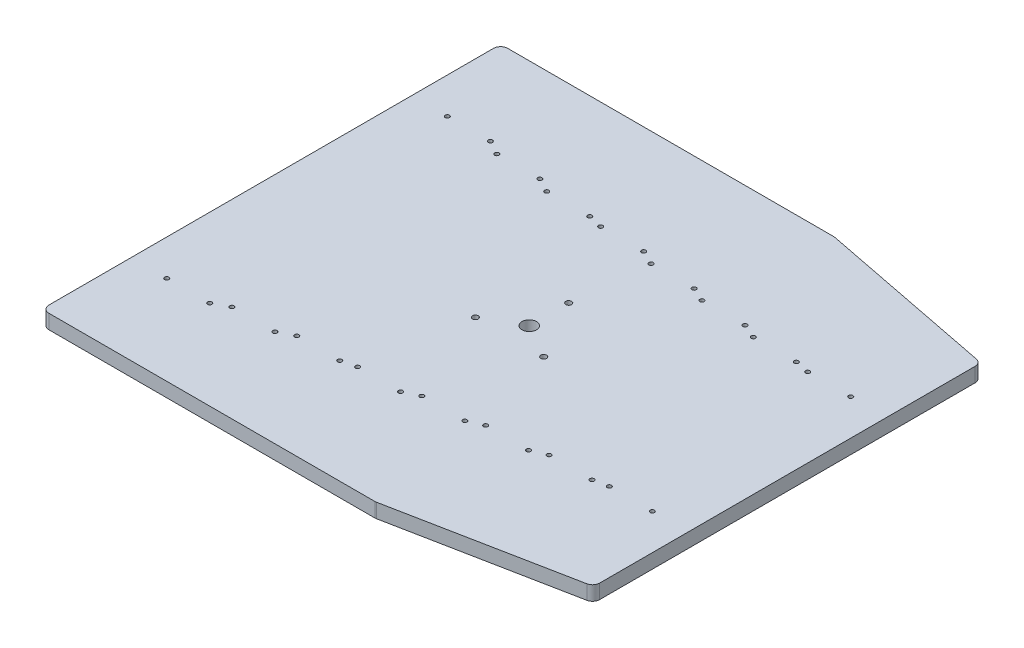
SolidWorks part; units mm, degrees
material "AISI Type 316L stainless steel"
ref_plane "Front Plane" through (0, 0, 0) normal (0, 0, 1) x (1, 0, 0)
ref_plane "Top Plane" through (0, 0, 0) normal (0, 1, 0) x (1, 0, 0)
ref_plane "Right Plane" through (0, 0, 0) normal (1, 0, 0) x (0, 0, -1)
sketch "Sketch1" plane through (0, 0, 0) normal (0, 1, 0) x (1, 0, 0)
  line L1 (-228.6, -203.2) -> (228.6, -203.2)
  line L2 (-228.6, -203.2) -> (-228.6, 203.2)
  line L3 (-228.6, 203.2) -> (228.6, 203.2)
  line L4 (228.6, -203.2) -> (228.6, 203.2)
  line L5 (-228.6, -203.2) -> (228.6, 203.2) construction
  line L6 (-228.6, 203.2) -> (228.6, -203.2) construction
  point P0 (0, 0)
  dimension "D1" = 457.2
  dimension "D2" = 406.4
extrude "Boss-Extrude1" add sketch "Sketch1" along normal blind 12.7
hole_wizard "#6 Clearance Hole1" positions "Sketch2" profile "Sketch3" hole size "#6" standard "ANSI Inch" end condition through all
sketch "Sketch2" plane through (0, 0, 0) normal (0, -1, 0) x (-1, 0, 0)
  line L0 (-228.6, 0) -> (228.6, 0) construction
  line L1 (-228.6, -203.2) -> (-228.6, 203.2) construction
  line L2 (228.6, 203.2) -> (228.6, -203.2) construction
  point P0 (-196.85, 87.8764)
  point P3 (-158.75, 87.8764)
  point P6 (-146.05, 90.4545)
  point P9 (-107.95, 90.4545)
  point P12 (-95.25, 95.8317)
  point P15 (-57.15, 95.8317)
  point P18 (-44.45, 101.5035)
  point P21 (-6.35, 101.5035)
  point P24 (6.35, 107.6173)
  point P27 (44.45, 107.6173)
  point P30 (57.15, 110.711)
  point P33 (95.25, 110.711)
  point P36 (107.95, 117.3404)
  point P39 (146.05, 117.3404)
  point P42 (158.75, 124.2644)
  point P45 (196.85, 124.2644)
  point P56 (196.85, -124.2644)
  point P57 (158.75, -124.2644)
  point P58 (146.05, -117.3404)
  point P59 (107.95, -117.3404)
  point P60 (95.25, -110.711)
  point P61 (57.15, -110.711)
  point P62 (44.45, -107.6173)
  point P63 (6.35, -107.6173)
  point P64 (-6.35, -101.5035)
  point P65 (-44.45, -101.5035)
  point P66 (-57.15, -95.8317)
  point P67 (-95.25, -95.8317)
  point P68 (-107.95, -90.4545)
  point P69 (-146.05, -90.4545)
  point P70 (-158.75, -87.8764)
  point P71 (-196.85, -87.8764)
sketch "Sketch3" plane through (196.85, 0, -87.8764) normal (1, 0, 0) x (0, 0, -1)
  line L0 (0, 0) -> (0, 12.7)
  line L1 (0, 12.7) -> (1.8986, 12.7)
  line L2 (1.8986, 12.7) -> (1.8986, 0)
  line L5 (1.8986, 0) -> (0, 0)
  line L11 (0, -6.35) -> (0, 107.95) construction
  dimension "Thru Hole Dia." = 3.7973
  dimension "Thru Hole Depth" = 12.7
sketch "Sketch4" plane through (0, 12.7, 0) normal (0, 1, 0) x (1, 0, 0)
  line L0 (-196.85, 124.2644) -> (-158.75, 124.2644) construction
  line L1 (-196.85, 130.6144) -> (-158.75, 130.6144)
  line L2 (-196.85, 117.9144) -> (-158.75, 117.9144)
  line L3 (-146.05, 117.3404) -> (-107.95, 117.3404) construction
  line L4 (-146.05, 123.6904) -> (-107.95, 123.6904)
  line L5 (-146.05, 110.9904) -> (-107.95, 110.9904)
  line L6 (-95.25, 110.711) -> (-57.15, 110.711) construction
  line L7 (-95.25, 117.061) -> (-57.15, 117.061)
  line L8 (-95.25, 104.361) -> (-57.15, 104.361)
  line L9 (-44.45, 107.6173) -> (-6.35, 107.6173) construction
  line L10 (-44.45, 113.9673) -> (-6.35, 113.9673)
  line L11 (-44.45, 101.2673) -> (-6.35, 101.2673)
  line L12 (6.35, 101.5035) -> (44.45, 101.5035) construction
  line L13 (6.35, 107.8535) -> (44.45, 107.8535)
  line L14 (6.35, 95.1535) -> (44.45, 95.1535)
  line L15 (57.15, 95.8317) -> (95.25, 95.8317) construction
  line L16 (57.15, 102.1817) -> (95.25, 102.1817)
  line L17 (57.15, 89.4817) -> (95.25, 89.4817)
  line L18 (107.95, 90.4545) -> (146.05, 90.4545) construction
  line L19 (107.95, 96.8045) -> (146.05, 96.8045)
  line L20 (107.95, 84.1045) -> (146.05, 84.1045)
  line L21 (158.75, 87.8764) -> (196.85, 87.8764) construction
  line L22 (158.75, 94.2264) -> (196.85, 94.2264)
  line L23 (158.75, 81.5264) -> (196.85, 81.5264)
  line L24 (-228.6, 0) -> (228.6, 0) construction
  line L25 (-228.6, 203.2) -> (-228.6, -203.2) construction
  line L26 (228.6, -203.2) -> (228.6, 203.2) construction
  line L27 (-196.85, -124.2644) -> (-158.75, -124.2644) construction
  line L28 (-196.85, -130.6144) -> (-158.75, -130.6144)
  line L29 (-196.85, -117.9144) -> (-158.75, -117.9144)
  line L30 (-146.05, -117.3404) -> (-107.95, -117.3404) construction
  line L31 (-146.05, -123.6904) -> (-107.95, -123.6904)
  line L32 (-146.05, -110.9904) -> (-107.95, -110.9904)
  line L33 (-95.25, -110.711) -> (-57.15, -110.711) construction
  line L34 (-95.25, -117.061) -> (-57.15, -117.061)
  line L35 (-95.25, -104.361) -> (-57.15, -104.361)
  line L36 (-44.45, -107.6173) -> (-6.35, -107.6173) construction
  line L37 (-44.45, -113.9673) -> (-6.35, -113.9673)
  line L38 (-44.45, -101.2673) -> (-6.35, -101.2673)
  line L39 (6.35, -101.5035) -> (44.45, -101.5035) construction
  line L40 (6.35, -107.8535) -> (44.45, -107.8535)
  line L41 (6.35, -95.1535) -> (44.45, -95.1535)
  line L42 (57.15, -95.8317) -> (95.25, -95.8317) construction
  line L43 (57.15, -102.1817) -> (95.25, -102.1817)
  line L44 (57.15, -89.4817) -> (95.25, -89.4817)
  line L45 (107.95, -90.4545) -> (146.05, -90.4545) construction
  line L46 (107.95, -96.8045) -> (146.05, -96.8045)
  line L47 (107.95, -84.1045) -> (146.05, -84.1045)
  line L48 (158.75, -87.8764) -> (196.85, -87.8764) construction
  line L49 (158.75, -94.2264) -> (196.85, -94.2264)
  line L50 (158.75, -81.5264) -> (196.85, -81.5264)
  arc A0 (-196.85, 130.6144) -> (-196.85, 117.9144) centre (-196.85, 124.2644) ccw
  arc A1 (-158.75, 117.9144) -> (-158.75, 130.6144) centre (-158.75, 124.2644) ccw
  arc A2 (-146.05, 123.6904) -> (-146.05, 110.9904) centre (-146.05, 117.3404) ccw
  arc A3 (-107.95, 110.9904) -> (-107.95, 123.6904) centre (-107.95, 117.3404) ccw
  arc A6 (-95.25, 117.061) -> (-95.25, 104.361) centre (-95.25, 110.711) ccw
  arc A7 (-57.15, 104.361) -> (-57.15, 117.061) centre (-57.15, 110.711) ccw
  arc A8 (-44.45, 113.9673) -> (-44.45, 101.2673) centre (-44.45, 107.6173) ccw
  arc A9 (-6.35, 101.2673) -> (-6.35, 113.9673) centre (-6.35, 107.6173) ccw
  arc A10 (6.35, 107.8535) -> (6.35, 95.1535) centre (6.35, 101.5035) ccw
  arc A11 (44.45, 95.1535) -> (44.45, 107.8535) centre (44.45, 101.5035) ccw
  arc A12 (57.15, 102.1817) -> (57.15, 89.4817) centre (57.15, 95.8317) ccw
  arc A13 (95.25, 89.4817) -> (95.25, 102.1817) centre (95.25, 95.8317) ccw
  arc A14 (107.95, 96.8045) -> (107.95, 84.1045) centre (107.95, 90.4545) ccw
  arc A15 (146.05, 84.1045) -> (146.05, 96.8045) centre (146.05, 90.4545) ccw
  arc A16 (158.75, 94.2264) -> (158.75, 81.5264) centre (158.75, 87.8764) ccw
  arc A17 (196.85, 81.5264) -> (196.85, 94.2264) centre (196.85, 87.8764) ccw
  circle A22 centre (196.85, 87.8764) radius 1.8987 construction
  arc A27 (-196.85, -130.6144) -> (-196.85, -117.9144) centre (-196.85, -124.2644) cw
  arc A28 (-158.75, -117.9144) -> (-158.75, -130.6144) centre (-158.75, -124.2644) cw
  arc A29 (-146.05, -123.6904) -> (-146.05, -110.9904) centre (-146.05, -117.3404) cw
  arc A30 (-107.95, -110.9904) -> (-107.95, -123.6904) centre (-107.95, -117.3404) cw
  arc A31 (-95.25, -117.061) -> (-95.25, -104.361) centre (-95.25, -110.711) cw
  arc A32 (-57.15, -104.361) -> (-57.15, -117.061) centre (-57.15, -110.711) cw
  arc A33 (-44.45, -113.9673) -> (-44.45, -101.2673) centre (-44.45, -107.6173) cw
  arc A34 (-6.35, -101.2673) -> (-6.35, -113.9673) centre (-6.35, -107.6173) cw
  arc A35 (6.35, -107.8535) -> (6.35, -95.1535) centre (6.35, -101.5035) cw
  arc A36 (44.45, -95.1535) -> (44.45, -107.8535) centre (44.45, -101.5035) cw
  arc A37 (57.15, -102.1817) -> (57.15, -89.4817) centre (57.15, -95.8317) cw
  arc A38 (95.25, -89.4817) -> (95.25, -102.1817) centre (95.25, -95.8317) cw
  arc A39 (107.95, -96.8045) -> (107.95, -84.1045) centre (107.95, -90.4545) cw
  arc A40 (146.05, -84.1045) -> (146.05, -96.8045) centre (146.05, -90.4545) cw
  arc A41 (158.75, -94.2264) -> (158.75, -81.5264) centre (158.75, -87.8764) cw
  arc A42 (196.85, -81.5264) -> (196.85, -94.2264) centre (196.85, -87.8764) cw
  point P4 (-177.8, 124.2644)
  point P16 (-127, 117.3404)
  point P27 (-76.2, 110.711)
  point P32 (-25.4, 107.6173)
  point P41 (25.4, 101.5035)
  point P50 (76.2, 95.8317)
  point P59 (127, 90.4545)
  point P68 (177.8, 87.8764)
  point P96 (-177.8, -124.2644)
  point P103 (-127, -117.3404)
  point P110 (-76.2, -110.711)
  point P117 (-25.4, -107.6173)
  point P124 (25.4, -101.5035)
  point P131 (76.2, -95.8317)
  point P138 (127, -90.4545)
  point P145 (177.8, -87.8764)
extrude "Cut-Extrude1" [suppressed] cut sketch "Sketch4" against normal blind 3.175
sketch "Sketch5" plane through (0, 0, 0) normal (0, -1, 0) x (1, 0, 0)
  line L0 (-228.6, -203.2) -> (228.6, 203.2) construction
  circle A0 centre (0, 0) radius 6.4135
  dimension "D1" = 12.827
extrude "Cut-Extrude2" cut sketch "Sketch5" against normal through all
sketch "Sketch6" plane through (0, 0, 0) normal (0, -1, 0) x (1, 0, 0)
  line L0 (-228.6, -203.2) -> (-228.6, 203.2) construction
  line L1 (-192.913, -121.9914) -> (-196.85, -119.7184)
  line L2 (-196.85, -119.7184) -> (-200.787, -121.9914)
  line L3 (-200.787, -121.9914) -> (-200.787, -126.5374)
  line L4 (-200.787, -126.5374) -> (-196.85, -128.8105)
  line L5 (-196.85, -128.8105) -> (-192.913, -126.5374)
  line L6 (-192.913, -126.5374) -> (-192.913, -121.9914)
  circle A0 centre (-196.85, -124.2644) radius 3.937 construction
  dimension "D1" = 7.874
extrude "Cut-Extrude3" cut sketch "Sketch6" against normal blind 3.175
pattern_sketch "Sketch-Pattern1" of "Cut-Extrude3" driven by "Sketch2"
hole_wizard "#10 Clearance Hole1" positions "Sketch7" profile "Sketch9" hole size "#10" standard "ANSI Inch" end condition through all
sketch "Sketch7" plane through (0, 12.7, 0) normal (0, 1, 0) x (1, 0, 0)
  line L0 (0, 0) -> (0, 34.925) construction
  line L5 (0, 0) -> (30.2459, -17.4625) construction
  line L6 (0, 0) -> (-30.2459, -17.4625) construction
  circle A0 centre (0, 0) radius 34.925 construction
  point P8 (0, 34.925)
  point P28 (30.2459, -17.4625)
  point P29 (-30.2459, -17.4625)
  dimension "D1" = 69.85
sketch "Sketch9" plane through (-30.2459, 12.7, 17.4625) normal (1, 0, 0) x (0, 0, 1)
  line L0 (0, 0) -> (0, 12.7)
  line L1 (0, 12.7) -> (2.5527, 12.7)
  line L2 (2.5527, 12.7) -> (2.5527, 0)
  line L5 (2.5527, 0) -> (0, 0)
  line L11 (0, -6.35) -> (0, 107.95) construction
  dimension "Thru Hole Dia." = 5.1054
  dimension "Thru Hole Depth" = 12.7
sketch "Sketch10" plane through (0, 12.7, 0) normal (0, 1, 0) x (1, 0, 0)
  line L0 (67.0352, -203.2) -> (228.6, -171.45)
  line L1 (-228.6, -203.2) -> (228.6, -203.2) construction
  line L2 (228.6, -203.2) -> (228.6, 203.2) construction
  line L3 (228.6, -171.45) -> (228.6, -203.2)
  line L4 (228.6, -203.2) -> (67.0352, -203.2)
  line L5 (228.6, 0) -> (-228.6, 0) construction
  line L6 (-228.6, 203.2) -> (-228.6, -203.2) construction
  line L7 (228.6, 203.2) -> (67.0352, 203.2)
  line L8 (228.6, 171.45) -> (228.6, 203.2)
  line L9 (67.0352, 203.2) -> (228.6, 171.45)
  circle A0 centre (196.85, 87.8764) radius 1.8987 construction
  point P18 (67.0352, -203.2)
  dimension "D1" = 31.75
extrude "Cut-Extrude4" cut sketch "Sketch10" against normal through all
fillet "Fillet1" radius 6.35 6 edges at (-228.6, 6.35, 203.2) (-228.6, 6.35, -203.2) (228.6, 6.35, -171.45) (228.6, 6.35, 171.45) (67.0352, 6.35, -203.2) (67.0352, 6.35, 203.2)
